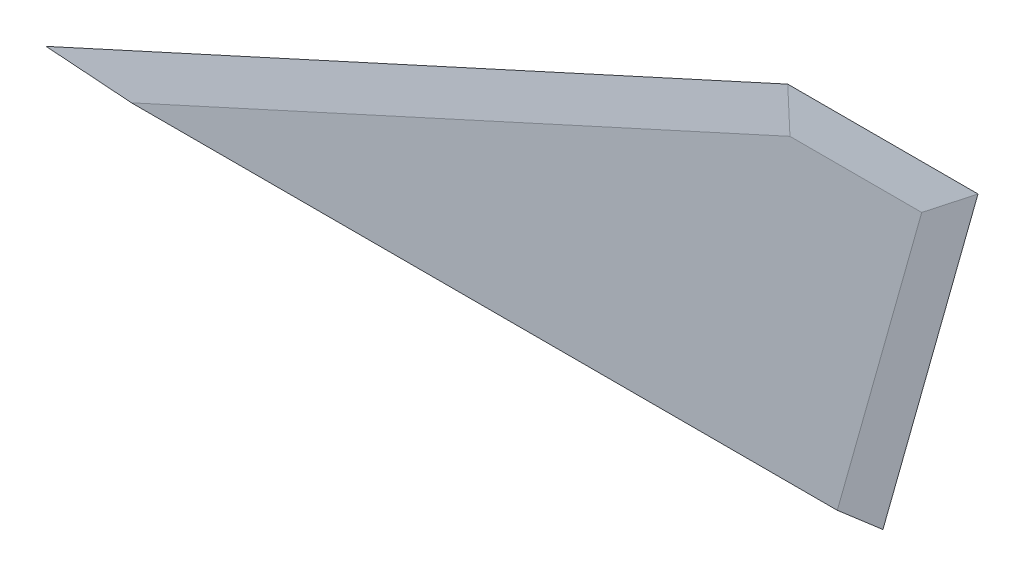
SolidWorks part; units mm, degrees
ref_plane "Front Plane" through (0, 0, 0) normal (0, 0, 1) x (1, 0, 0)
ref_plane "Top Plane" through (0, 0, 0) normal (0, 1, 0) x (1, 0, 0)
ref_plane "Right Plane" through (0, 0, 0) normal (1, 0, 0) x (0, 0, -1)
sketch "Sketch1" plane through (0, 0, 0) normal (0, 0, 1) x (1, 0, 0)
  line L0 (0, 0) -> (220, 0)
  line L1 (220, 0) -> (245, 88.9)
  line L2 (245, 88.9) -> (195, 88.9)
  line L3 (195, 88.9) -> (0, 0)
  dimension "D1" = 220
  dimension "D2" = 50
  dimension "D3" = 195
  dimension "D4" = 88.9
extrude "Boss-Extrude1" add sketch "Sketch1" along normal mid plane 3.18
chamfer "Chamfer1" distance 1.59 distance2 10 3 edges at (232.5, 44.45, 1.59) (220, 88.9, 1.59) (97.5, 44.45, 1.59) first distance on face at (232.5, 44.45, 0) first distance on face at (220, 88.9, 0) first distance on face at (97.5, 44.45, 0)
chamfer "Chamfer2" distance 10 distance2 1.59 3 edges at (97.5, 44.45, -1.59) (220, 88.9, -1.59) (232.5, 44.45, -1.59) first distance on face at (165, 44.45, -1.59)
sketch "Sketch2" plane through (0, 0, 0) normal (1, 0, 0) x (0, 0, -1)
  circle A0 centre (0, -40.9692) radius 41
  dimension "D1" = 82
extrude "Cut-Extrude1" cut sketch "Sketch2" along normal blind 220
